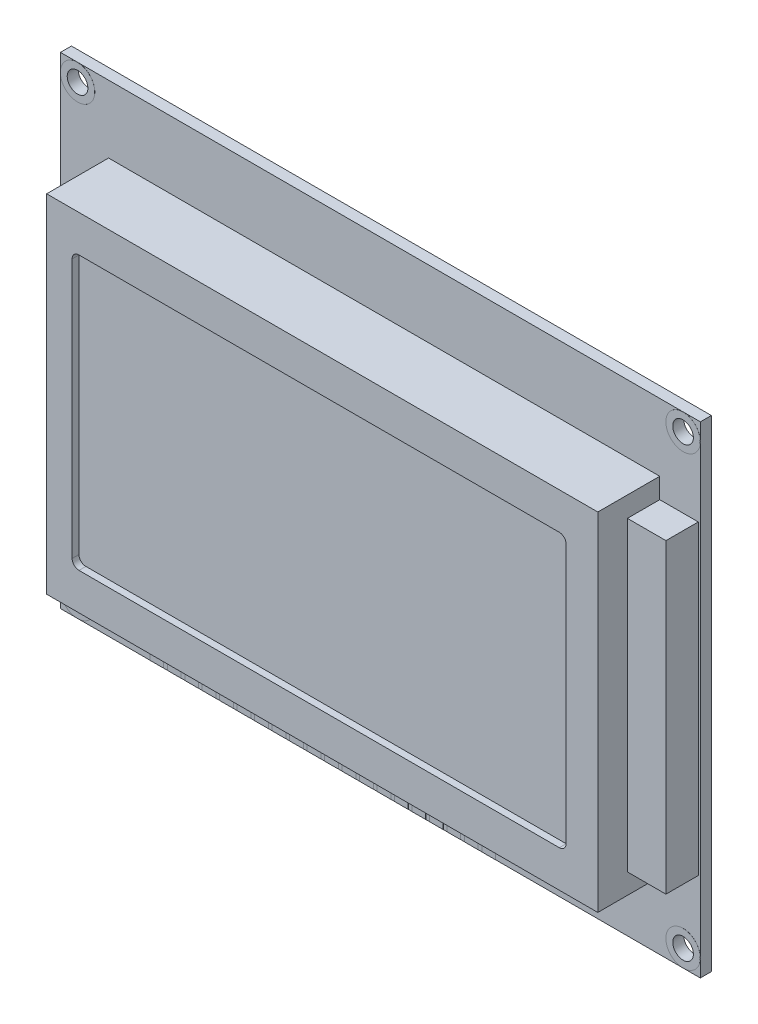
SolidWorks part; units mm, degrees
ref_plane "Front" through (0, 0, 0) normal (0, 0, 1) x (1, 0, 0)
ref_plane "Top" through (0, 0, 0) normal (0, 1, 0) x (1, 0, 0)
ref_plane "Right" through (0, 0, 0) normal (1, 0, 0) x (0, 0, -1)
sketch "Sketch1" plane through (0, 0, 0) normal (0, 0, 1) x (1, 0, 0)
  line L0 (0, 35) -> (0, -35) construction
  line L1 (-46.5, 35) -> (46.5, 35)
  line L2 (-46.5, 35) -> (-46.5, -35)
  line L3 (-46.5, -35) -> (46.5, -35)
  line L4 (46.5, 35) -> (46.5, -35)
  point P6 (0, 0)
  dimension "D1" = 93
  dimension "D2" = 70
extrude "base pcb" add sketch "Sketch1" along normal blind 1.6
sketch "Sketch2" plane through (0, 0, 1.6) normal (0, 0, 1) x (1, 0, 0)
  line L0 (0, 32.5) -> (0, -32.5) construction
  line L1 (-44, 32.5) -> (44, 32.5) construction
  line L2 (-44, 32.5) -> (-44, -32.5) construction
  line L3 (-44, -32.5) -> (44, -32.5) construction
  line L4 (44, 32.5) -> (44, -32.5) construction
  circle A0 centre (-44, 32.5) radius 1.5
  circle A1 centre (-44, -32.5) radius 1.5
  circle A2 centre (44, -32.5) radius 1.5
  circle A3 centre (44, 32.5) radius 1.5
  point P6 (0, 0)
  dimension "D3" = 3
  dimension "D1" = 65
  dimension "D2" = 88
extrude "mount hole" cut sketch "Sketch2" against normal through all
sketch "Sketch3" plane through (0, 0, 1.6) normal (0, 0, 1) x (1, 0, 0)
  line L0 (-46.5, -35) -> (46.5, -35) construction
  line L1 (-46.5, 35) -> (-46.5, -35) construction
  circle A0 centre (-32.5, -32.5) radius 0.5
  circle A19 centre (-29.96, -32.5) radius 0.5
  circle A20 centre (-27.42, -32.5) radius 0.5
  circle A21 centre (-24.88, -32.5) radius 0.5
  circle A22 centre (-22.34, -32.5) radius 0.5
  circle A23 centre (-19.8, -32.5) radius 0.5
  circle A24 centre (-17.26, -32.5) radius 0.5
  circle A25 centre (-14.72, -32.5) radius 0.5
  circle A26 centre (-12.18, -32.5) radius 0.5
  circle A27 centre (-9.64, -32.5) radius 0.5
  circle A28 centre (-7.1, -32.5) radius 0.5
  circle A29 centre (-4.56, -32.5) radius 0.5
  circle A30 centre (-2.02, -32.5) radius 0.5
  circle A31 centre (0.52, -32.5) radius 0.5
  circle A32 centre (3.06, -32.5) radius 0.5
  circle A33 centre (5.6, -32.5) radius 0.5
  circle A34 centre (8.14, -32.5) radius 0.5
  circle A35 centre (10.68, -32.5) radius 0.5
  circle A36 centre (13.22, -32.5) radius 0.5
  circle A37 centre (15.76, -32.5) radius 0.5
  dimension "D1" = 2.5
  dimension "D3" = 1
  dimension "D2" = 14
extrude "pin" cut sketch "Sketch3" against normal through all
sketch "Sketch4" plane through (0, 0, 1.6) normal (0, 0, 1) x (1, 0, 0)
  line L0 (-33.5, -32.5) -> (-33.5, -35)
  line L1 (-46.5, -35) -> (46.5, -35) construction
  line L2 (-31.5, -32.5) -> (-31.5, -35)
  line L3 (-33.5, -35) -> (-31.5, -35)
  line L4 (-30.96, -32.5) -> (-30.96, -35)
  line L5 (-28.96, -32.5) -> (-28.96, -35)
  line L6 (-30.96, -35) -> (-28.96, -35)
  line L7 (-28.42, -32.5) -> (-28.42, -35)
  line L8 (-26.42, -32.5) -> (-26.42, -35)
  line L9 (-28.42, -35) -> (-26.42, -35)
  line L10 (-25.88, -32.5) -> (-25.88, -35)
  line L11 (-23.88, -32.5) -> (-23.88, -35)
  line L12 (-25.88, -35) -> (-23.88, -35)
  line L13 (-23.34, -32.5) -> (-23.34, -35)
  line L14 (-21.34, -32.5) -> (-21.34, -35)
  line L15 (-23.34, -35) -> (-21.34, -35)
  line L16 (-20.8, -32.5) -> (-20.8, -35)
  line L17 (-18.8, -32.5) -> (-18.8, -35)
  line L18 (-20.8, -35) -> (-18.8, -35)
  line L19 (-18.26, -32.5) -> (-18.26, -35)
  line L20 (-16.26, -32.5) -> (-16.26, -35)
  line L21 (-18.26, -35) -> (-16.26, -35)
  line L22 (-15.72, -32.5) -> (-15.72, -35)
  line L23 (-13.72, -32.5) -> (-13.72, -35)
  line L24 (-15.72, -35) -> (-13.72, -35)
  line L25 (-13.18, -32.5) -> (-13.18, -35)
  line L26 (-11.18, -32.5) -> (-11.18, -35)
  line L27 (-13.18, -35) -> (-11.18, -35)
  line L28 (-10.64, -32.5) -> (-10.64, -35)
  line L29 (-8.64, -32.5) -> (-8.64, -35)
  line L30 (-10.64, -35) -> (-8.64, -35)
  line L31 (-8.1, -32.5) -> (-8.1, -35)
  line L32 (-6.1, -32.5) -> (-6.1, -35)
  line L33 (-8.1, -35) -> (-6.1, -35)
  line L34 (-5.56, -32.5) -> (-5.56, -35)
  line L35 (-3.56, -32.5) -> (-3.56, -35)
  line L36 (-5.56, -35) -> (-3.56, -35)
  line L37 (-3.02, -32.5) -> (-3.02, -35)
  line L38 (-1.02, -32.5) -> (-1.02, -35)
  line L39 (-3.02, -35) -> (-1.02, -35)
  line L40 (-0.48, -32.5) -> (-0.48, -35)
  line L41 (1.52, -32.5) -> (1.52, -35)
  line L42 (-0.48, -35) -> (1.52, -35)
  line L43 (2.06, -32.5) -> (2.06, -35)
  line L44 (4.06, -32.5) -> (4.06, -35)
  line L45 (2.06, -35) -> (4.06, -35)
  line L46 (4.6, -32.5) -> (4.6, -35)
  line L47 (6.6, -32.5) -> (6.6, -35)
  line L48 (4.6, -35) -> (6.6, -35)
  line L49 (7.14, -32.5) -> (7.14, -35)
  line L50 (9.14, -32.5) -> (9.14, -35)
  line L51 (7.14, -35) -> (9.14, -35)
  line L52 (9.68, -32.5) -> (9.68, -35)
  line L53 (11.68, -32.5) -> (11.68, -35)
  line L54 (9.68, -35) -> (11.68, -35)
  line L55 (12.22, -32.5) -> (12.22, -35)
  line L56 (14.22, -32.5) -> (14.22, -35)
  line L57 (12.22, -35) -> (14.22, -35)
  line L58 (14.76, -32.5) -> (14.76, -35)
  line L59 (16.76, -32.5) -> (16.76, -35)
  line L60 (14.76, -35) -> (16.76, -35)
  circle A0 centre (-44, 32.5) radius 2.5
  circle A1 centre (44, 32.5) radius 2.5
  circle A2 centre (44, -32.5) radius 2.5
  circle A3 centre (-44, -32.5) radius 2.5
  arc A4 (-33.5, -32.5) -> (-31.5, -32.5) centre (-32.5, -32.5) cw
  circle A7 centre (-32.5, -32.5) radius 0.5 construction
  circle A8 centre (-32.5, -32.5) radius 0.5
  arc A9 (-30.96, -32.5) -> (-28.96, -32.5) centre (-29.96, -32.5) cw
  circle A10 centre (-29.96, -32.5) radius 0.5
  arc A11 (-28.42, -32.5) -> (-26.42, -32.5) centre (-27.42, -32.5) cw
  circle A12 centre (-27.42, -32.5) radius 0.5
  arc A13 (-25.88, -32.5) -> (-23.88, -32.5) centre (-24.88, -32.5) cw
  circle A14 centre (-24.88, -32.5) radius 0.5
  arc A15 (-23.34, -32.5) -> (-21.34, -32.5) centre (-22.34, -32.5) cw
  circle A16 centre (-22.34, -32.5) radius 0.5
  arc A17 (-20.8, -32.5) -> (-18.8, -32.5) centre (-19.8, -32.5) cw
  circle A18 centre (-19.8, -32.5) radius 0.5
  arc A19 (-18.26, -32.5) -> (-16.26, -32.5) centre (-17.26, -32.5) cw
  circle A20 centre (-17.26, -32.5) radius 0.5
  arc A21 (-15.72, -32.5) -> (-13.72, -32.5) centre (-14.72, -32.5) cw
  circle A22 centre (-14.72, -32.5) radius 0.5
  arc A23 (-13.18, -32.5) -> (-11.18, -32.5) centre (-12.18, -32.5) cw
  circle A24 centre (-12.18, -32.5) radius 0.5
  arc A25 (-10.64, -32.5) -> (-8.64, -32.5) centre (-9.64, -32.5) cw
  circle A26 centre (-9.64, -32.5) radius 0.5
  arc A27 (-8.1, -32.5) -> (-6.1, -32.5) centre (-7.1, -32.5) cw
  circle A28 centre (-7.1, -32.5) radius 0.5
  arc A29 (-5.56, -32.5) -> (-3.56, -32.5) centre (-4.56, -32.5) cw
  circle A30 centre (-4.56, -32.5) radius 0.5
  arc A31 (-3.02, -32.5) -> (-1.02, -32.5) centre (-2.02, -32.5) cw
  circle A32 centre (-2.02, -32.5) radius 0.5
  arc A33 (-0.48, -32.5) -> (1.52, -32.5) centre (0.52, -32.5) cw
  circle A34 centre (0.52, -32.5) radius 0.5
  arc A35 (2.06, -32.5) -> (4.06, -32.5) centre (3.06, -32.5) cw
  circle A36 centre (3.06, -32.5) radius 0.5
  arc A37 (4.6, -32.5) -> (6.6, -32.5) centre (5.6, -32.5) cw
  circle A38 centre (5.6, -32.5) radius 0.5
  arc A39 (7.14, -32.5) -> (9.14, -32.5) centre (8.14, -32.5) cw
  circle A40 centre (8.14, -32.5) radius 0.5
  arc A41 (9.68, -32.5) -> (11.68, -32.5) centre (10.68, -32.5) cw
  circle A42 centre (10.68, -32.5) radius 0.5
  arc A43 (12.22, -32.5) -> (14.22, -32.5) centre (13.22, -32.5) cw
  circle A44 centre (13.22, -32.5) radius 0.5
  arc A45 (14.76, -32.5) -> (16.76, -32.5) centre (15.76, -32.5) cw
  circle A46 centre (15.76, -32.5) radius 0.5
  dimension "D1" = 5
extrude "gild" add sketch "Sketch4" along normal blind 0.01
sketch "Sketch5" plane through (0, 0, 1.6) normal (0, 0, 1) x (1, 0, 0)
  line L0 (0.55, 25.2) -> (0.55, -25.2) construction
  line L1 (-39.5, 25.2) -> (40.6, 25.2)
  line L2 (-39.5, 25.2) -> (-39.5, -25.2)
  line L3 (-39.5, -25.2) -> (40.6, -25.2)
  line L4 (40.6, 25.2) -> (40.6, -25.2)
  line L5 (-46.5, 0) -> (-39.5, 0) construction
  line L6 (-46.5, 32.5) -> (-46.5, -32.5) construction
  line L7 (46.5, -32.5) -> (46.5, 32.5) construction
  point P6 (0.55, 0)
  dimension "D1" = 50.4
  dimension "D2" = 80.1
  dimension "D3" = 7
  dimension "D4" = 5.9
extrude "metal shield" add sketch "Sketch5" along normal blind 9
sketch "Sketch6" plane through (0, 0, 10.6) normal (0, 0, 1) x (1, 0, 0)
  line L0 (0.1, -19.85) -> (0.1, 19.85) construction
  line L1 (-34.8, 19.85) -> (35, 19.85)
  line L2 (-35.8, 18.85) -> (-35.8, -18.85)
  line L3 (-34.8, -19.85) -> (35, -19.85)
  line L4 (36, 18.85) -> (36, -18.85)
  line L6 (40.6, -25.2) -> (40.6, 25.2) construction
  line L7 (-39.5, 25.2) -> (-39.5, -25.2) construction
  line L8 (-39.5, 0) -> (-35.8, 0) construction
  line L9 (-39.5, 25.2) -> (-39.5, -25.2) construction
  arc A0 (-34.8, 19.85) -> (-35.8, 18.85) centre (-34.8, 18.85) ccw
  arc A1 (-34.8, -19.85) -> (-35.8, -18.85) centre (-34.8, -18.85) cw
  arc A2 (36, -18.85) -> (35, -19.85) centre (35, -18.85) cw
  arc A3 (36, 18.85) -> (35, 19.85) centre (35, 18.85) ccw
  point P6 (0.1, 0)
  point P10 (-35.8, 19.85)
  point P13 (-35.8, -19.85)
  point P18 (36, 19.85)
  dimension "D3" = 1
  dimension "D1" = 71.8
  dimension "D2" = 39.7
  dimension "D4" = 4.6
  dimension "D5" = 3.7
extrude "glass" cut sketch "Sketch6" against normal blind 1
sketch "Sketch9" plane through (0, 0, 1.6) normal (0, 0, 1) x (1, 0, 0)
  line L0 (40.6, -25.2) -> (40.6, 25.2) construction
  line L1 (40.6, 22.25) -> (46.2, 22.25)
  line L2 (40.6, 22.25) -> (40.6, -22.25)
  line L3 (40.6, -22.25) -> (46.2, -22.25)
  line L4 (46.2, 22.25) -> (46.2, -22.25)
  line L5 (46.2, 0) -> (46.5, 0) construction
  line L6 (46.5, -32.5) -> (46.5, 32.5) construction
  dimension "D1" = 44.5
  dimension "D2" = 0.3
extrude "backlight" add sketch "Sketch9" along normal blind 4.7
sketch "Sketch7" plane through (0, 0, 0) normal (0, 0, -1) x (-1, 0, 0)
  line L0 (-36.0625, 25.1717) -> (-32.1147, 21.7309)
  line L1 (-32.1147, 21.7309) -> (-31.5555, 22.3725)
  line L2 (-31.5555, 22.3725) -> (-35.5033, 25.8133)
  line L3 (-35.5033, 25.8133) -> (-36.0625, 25.1717)
extrude "shield_clip" add sketch "Sketch7" along normal blind 2.6
pattern_linear "LPattern1" count 4 spacing 22 along (-1, 0, 0) of "shield_clip"
sketch "Sketch8" plane through (0, 0, 0) normal (0, 0, -1) x (-1, 0, 0)
  circle A0 centre (-16.5168, 2.639) radius 7
  circle A1 centre (5.2615, 4.2456) radius 7.3662
  circle A2 centre (26.0068, 1.0646) radius 7.7451
extrude "IC" add sketch "Sketch8" along normal blind 2
fillet "IC fillet" radius 10.5 3 edges at (-33.7519, 1.0646, -2) (-12.6277, 4.2456, -2) (9.5168, 2.639, -2)
